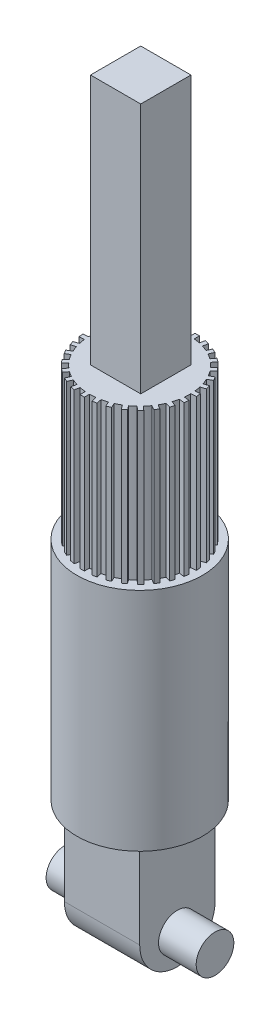
SolidWorks part; units mm, degrees
ref_plane "Front Plane" through (0, 0, 0) normal (0, 0, 1) x (1, 0, 0)
ref_plane "Top Plane" through (0, 0, 0) normal (0, 1, 0) x (1, 0, 0)
ref_plane "Right Plane" through (0, 0, 0) normal (1, 0, 0) x (0, 0, -1)
sketch "Sketch1" plane through (0, 0, 0) normal (0, 1, 0) x (1, 0, 0)
  circle A0 centre (0, 0) radius 2
  dimension "D1" = 4
extrude "Boss-Extrude1" add sketch "Sketch1" along normal blind 6
sketch "Sketch5" plane through (0, 6, 0) normal (0, 1, 0) x (1, 0, 0)
  line L0 (0, -2) -> (-0.1765, -1.9922)
  line L1 (-0.1765, -1.9922) -> (-0.1765, -2.2025)
  line L2 (-0.1765, -2.2025) -> (0, -2.2025)
  line L3 (0, -2.2025) -> (0, -2)
  circle A0 centre (0, 0) radius 2 construction
extrude "Boss-Extrude3" add sketch "Sketch5" against normal blind 6
pattern_circular "CirPattern1" count 30 over 360 about axis through (0, 6, 0) along (0, -1, 0) of "Boss-Extrude3"
sketch "Sketch9" plane through (0, 0, 0) normal (0, -1, 0) x (1, 0, 0)
  circle A0 centre (0, 0) radius 2.5
extrude "Boss-Extrude5" add sketch "Sketch9" along normal blind 9
sketch "Sketch10" plane through (0, 6, 0) normal (0, 1, 0) x (1, 0, 0)
  line L1 (1.0097, -0.9683) -> (-0.9903, -0.9683)
  line L2 (1.0097, -0.9683) -> (1.0097, 1.0317)
  line L3 (1.0097, 1.0317) -> (-0.9903, 1.0317)
  line L4 (-0.9903, -0.9683) -> (-0.9903, 1.0317)
extrude "Boss-Extrude6" add sketch "Sketch10" along normal blind 10
sketch "Sketch11" plane through (0, -9, 0) normal (0, -1, 0) x (1, 0, 0)
  line L1 (-1.5, 1.5) -> (1.5, 1.5)
  line L2 (-1.5, 1.5) -> (-1.5, -1.5)
  line L3 (-1.5, -1.5) -> (1.5, -1.5)
  line L4 (1.5, 1.5) -> (1.5, -1.5)
extrude "Boss-Extrude7" add sketch "Sketch11" along normal blind 5
fillet "Fillet1" 2 edges at (0, -14, 1.5) (0, -14, -1.5) type full round first side face at (0, -11.5, 1.5) second side face at (0, -11.5, -1.5) middle face at (0, -14, 0)
sketch "Sketch12" plane through (1.5, 0, 0) normal (1, 0, 0) x (0, 0, -1)
  circle A0 centre (0, -12.8) radius 0.75
  arc A1 (-1.5, -12.5) -> (1.5, -12.5) centre (0, -12.5) ccw construction
  point P2 (0, -14)
extrude "Boss-Extrude9" add sketch "Sketch12" along normal blind 1.5 and the other way blind 4.4771
